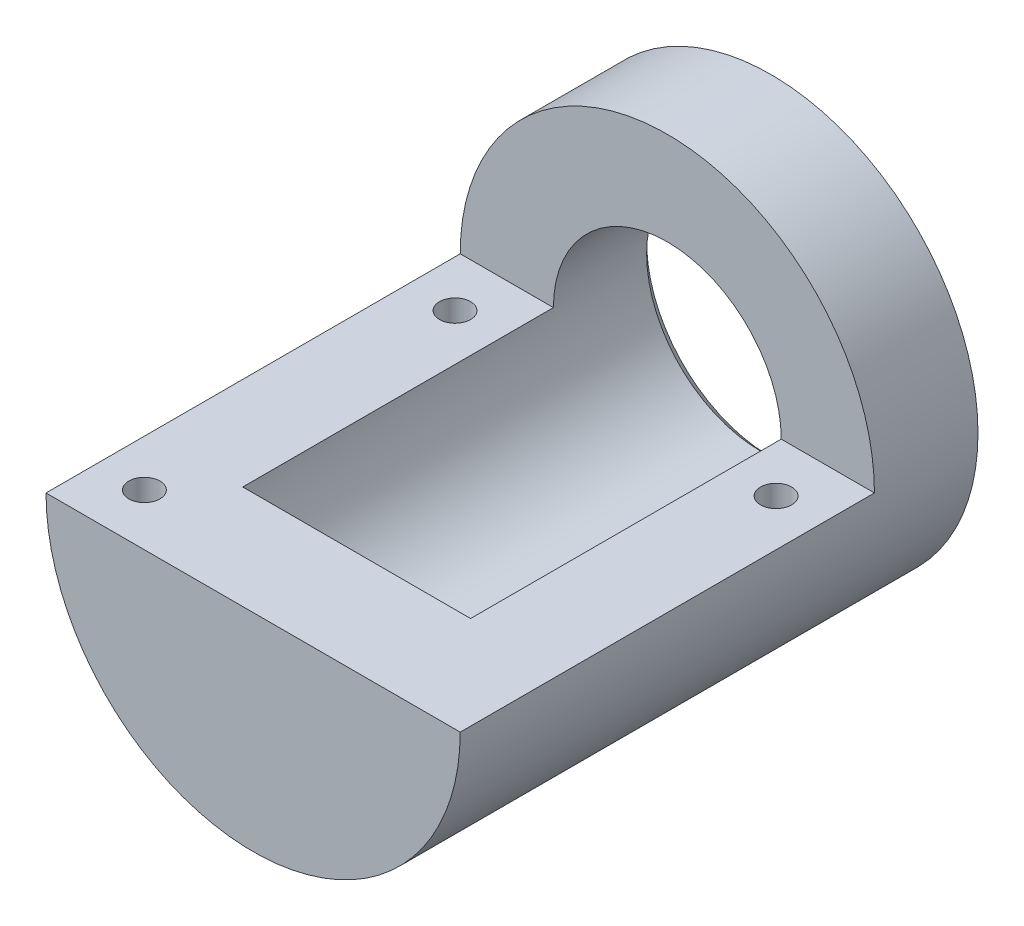
SolidWorks part; units mm, degrees
ref_plane "Front Plane" through (0, 0, 0) normal (0, 0, 1) x (1, 0, 0)
ref_plane "Top Plane" through (0, 0, 0) normal (0, 1, 0) x (1, 0, 0)
ref_plane "Right Plane" through (0, 0, 0) normal (1, 0, 0) x (0, 0, -1)
sketch "Sketch1" plane through (0, 0, 0) normal (0, 0, 1) x (1, 0, 0)
  circle A0 centre (0, 0) radius 11
  circle A1 centre (0, 0) radius 4
  circle A2 centre (0, 0) radius 20
  dimension "D1" = 22
  dimension "D2" = 8
  dimension "D3" = 9
extrude "Boss-Extrude1" add sketch "Sketch1" along normal blind 10 contours A2 | A0
sketch "Sketch2" plane through (0, 0, 10) normal (0, 0, 1) x (1, 0, 0)
  line L0 (-20, 0) -> (-11, 0)
  line L1 (11, 0) -> (20, 0)
  arc A0 (-20, 0) -> (20, 0) centre (0, 0) ccw
  arc A1 (-11, 0) -> (11, 0) centre (0, 0) ccw
  circle A2 centre (0, 0) radius 11 construction
  circle A3 centre (0, 0) radius 20 construction
extrude "Boss-Extrude3" add sketch "Sketch2" along normal blind 40
sketch "Sketch3" plane through (0, 0, 50) normal (0, 0, 1) x (1, 0, 0)
  line L0 (-20, 0) -> (20, 0)
  arc A0 (-20, 0) -> (20, 0) centre (0, 0) ccw
  arc A4 (-20, 0) -> (20, 0) centre (0, 0) ccw construction
extrude "Boss-Extrude4" add sketch "Sketch3" against normal blind 10
fillet "Chamfer2" radius 1 1 edges at (11, 0, 0) type face fillet profile chamfer first side face at (20, 0, 0) second side face at (11, 0, 0)
sketch "Sketch4" plane through (0, 0, 0) normal (0, 1, 0) x (1, 0, 0)
  line L0 (-20, -10) -> (20, -10) construction
  line L1 (-20, -50) -> (-20, -10) construction
  line L2 (20, -50) -> (20, -10) construction
  line L3 (20, -50) -> (-20, -50) construction
  circle A0 centre (-15.5, -15) radius 1.5
  circle A1 centre (15.5, -15) radius 1.5
  circle A2 centre (-15.5, -45) radius 1.5
  dimension "D7" = 3
  dimension "D8" = 3
  dimension "D9" = 3
  dimension "D1" = 5
  dimension "D2" = 4.5
  dimension "D3" = 5
  dimension "D4" = 4.5
  dimension "D5" = 5
  dimension "D6" = 4.5
extrude "Cut-Extrude1" cut sketch "Sketch4" against normal blind 8
